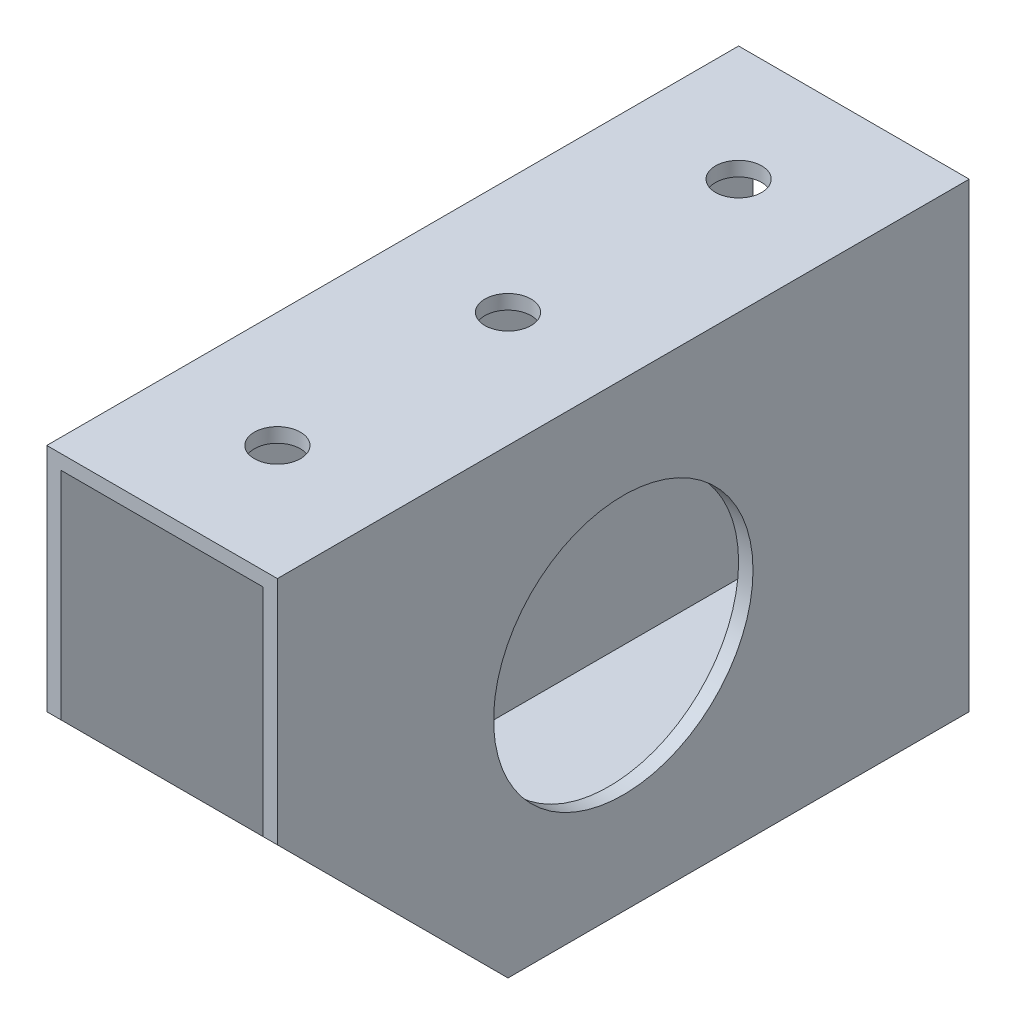
SolidWorks part; units mm, degrees
ref_plane "Front Plane" through (0, 0, 0) normal (0, 0, 1) x (1, 0, 0)
ref_plane "Top Plane" through (0, 0, 0) normal (0, 1, 0) x (1, 0, 0)
ref_plane "Right Plane" through (0, 0, 0) normal (1, 0, 0) x (0, 0, -1)
sketch "Sketch1" plane through (0, 0, 0) normal (0, 0, 1) x (1, 0, 0)
  line L1 (0, 0) -> (25.4, 0)
  line L2 (0, 0) -> (0, 50.8)
  line L3 (0, 50.8) -> (25.4, 50.8)
  line L4 (25.4, 0) -> (25.4, 50.8)
  line L5 (1.5875, 1.5875) -> (23.8125, 1.5875)
  line L6 (1.5875, 1.5875) -> (1.5875, 49.2125)
  line L7 (1.5875, 49.2125) -> (23.8125, 49.2125)
  line L8 (23.8125, 1.5875) -> (23.8125, 49.2125)
  dimension "D1" = 25.4
  dimension "D2" = 50.8
  dimension "D3" = 1.5875
  dimension "D4" = 1.5875
  dimension "D5" = 1.5875
  dimension ".0625" = 1.5875
extrude "Boss-Extrude1" add sketch "Sketch1" along normal blind 76.2
sketch "Sketch2" plane through (25.4, 0, 0) normal (1, 0, 0) x (0, 0, -1)
  line L3 (-76.2, 50.8) -> (0, 50.8) construction
  line L4 (0, 0) -> (0, 50.8) construction
  circle A43 centre (-38.1, 25.4) radius 14.2875
  dimension "D1" = 28.575
  dimension "D2" = 25.4
  dimension "1" = 38.1
extrude "Cut-Extrude1" cut sketch "Sketch2" against normal through all
sketch "Sketch3" plane through (25.4, 0, 0) normal (1, 0, 0) x (0, 0, -1)
  line L0 (-50.8, 0) -> (-76.2, 25.4)
  line L1 (-76.2, 0) -> (0, 0) construction
  line L2 (-76.2, 0) -> (-76.2, 50.8) construction
  line L3 (-76.2, 25.4) -> (-76.2, 0)
  line L4 (-76.2, 0) -> (-50.8, 0)
  dimension "D1" = 25.4
extrude "Cut-Extrude2" cut sketch "Sketch3" against normal through all
sketch "Sketch4" plane through (0, 50.8, 0) normal (0, 1, 0) x (1, 0, 0)
  line L0 (25.4, -76.2) -> (25.4, 0) construction
  line L1 (25.4, 0) -> (0, 0) construction
  circle A0 centre (12.7, -12.7) radius 2.54
  circle A1 centre (12.7, -38.1) radius 2.54
  circle A2 centre (12.7, -63.5) radius 2.54
  dimension "D1" = 5.08
  dimension "D2" = 12.7
  dimension "D3" = 12.7
  dimension "D4" = 25.4
  dimension "D5" = 25.4
extrude "Cut-Extrude3" cut sketch "Sketch4" against normal up to next
sketch "Sketch5" plane through (0, 0, 0) normal (0, -1, 0) x (1, 0, 0)
  line L0 (12.7, 50.8) -> (12.7, 0) construction
  line L1 (0, 50.8) -> (25.4, 50.8) construction
  line L2 (0, 0) -> (25.4, 0) construction
  circle A0 centre (12.7, 12.7) radius 2.54
  circle A1 centre (12.7, 39.6875) radius 2.54
  dimension "D3" = 5.08
  dimension "D1" = 12.7
  dimension "D2" = 26.9875
extrude "Cut-Extrude4" cut sketch "Sketch5" against normal up to next
